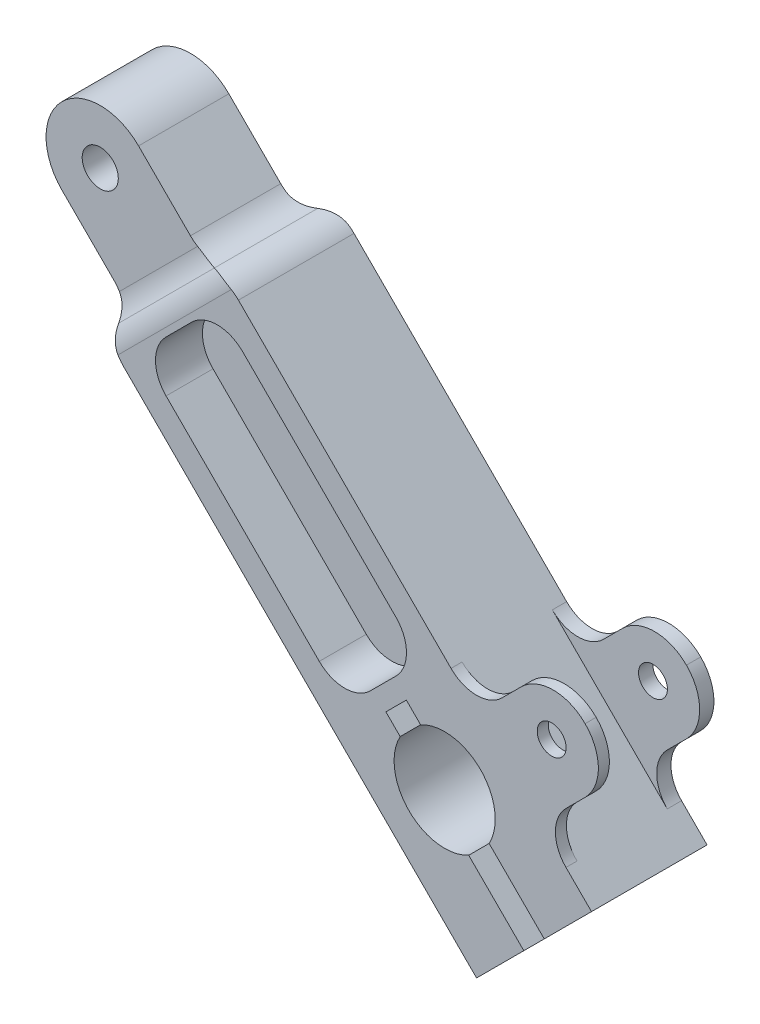
SolidWorks part; units mm, degrees
ref_plane "Front Plane" through (0, 0, 0) normal (0, 0, 1) x (1, 0, 0)
ref_plane "Top Plane" through (0, 0, 0) normal (0, 1, 0) x (1, 0, 0)
ref_plane "Right Plane" through (0, 0, 0) normal (1, 0, 0) x (0, 0, -1)
sketch "Sketch2" plane through (0, 0, 0) normal (0, 0, 1) x (1, 0, 0)
  line L0 (0, 0) -> (-234.0257, 0) construction
  line L1 (0, 0) -> (132.15, 132.15) construction
  line L2 (0, 0) -> (130.2279, -130.2279) construction
  line L3 (-10.6066, -10.6066) -> (10.6066, 10.6066) construction
  line L4 (-10.6066, -10.6066) -> (21.2132, -42.4264) construction
  line L5 (21.2132, -42.4264) -> (42.4264, -21.2132) construction
  line L6 (42.4264, -21.2132) -> (10.6066, 10.6066) construction
  line L7 (0, -21.2132) -> (21.2132, 0)
  line L9 (21.2132, 0) -> (53.033, -31.8198)
  line L10 (0, -21.2132) -> (31.8198, -53.033)
  line L11 (31.8198, -53.033) -> (26.5165, -58.3363)
  line L12 (114.318, -146.1378) -> (26.5165, -58.3363)
  line L13 (53.033, -31.8198) -> (58.3363, -26.5165)
  line L14 (128.4601, -96.6403) -> (58.3363, -26.5165)
  line L15 (146.1378, -114.318) -> (167.351, -93.1047)
  line L16 (167.351, -93.1047) -> (149.6733, -75.4271)
  line L17 (149.6733, -75.4271) -> (128.4601, -96.6403)
  line L18 (158.5121, -84.2659) -> (119.6213, -119.6213) construction
  line L19 (146.1378, -114.318) -> (160.2799, -128.4601)
  line L20 (114.318, -146.1378) -> (128.4601, -160.2799)
  line L21 (160.2799, -128.4601) -> (147.1984, -141.5416)
  line L22 (109.0147, -103.3578) -> (112.9628, -107.306)
  line L23 (103.3578, -109.0147) -> (109.0147, -103.3578)
  line L24 (103.3578, -109.0147) -> (107.306, -112.9628)
  line L25 (131.9365, -126.2797) -> (147.1984, -141.5416)
  line L26 (126.2797, -131.9365) -> (141.5416, -147.1984)
  line L27 (141.5416, -147.1984) -> (128.4601, -160.2799)
  line L28 (31.8198, -53.033) -> (53.033, -31.8198)
  line L29 (128.4601, -96.6403) -> (146.1378, -114.318)
  circle A0 centre (21.2132, -21.2132) radius 5
  circle A1 centre (149.2524, -92.6839) radius 4
  arc A2 (107.306, -112.9628) -> (126.2797, -131.9365) centre (119.6213, -119.6213) ccw
  arc A3 (131.9365, -126.2797) -> (112.9628, -107.306) centre (119.6213, -119.6213) ccw
  point P8 (0, 0)
  point P15 (10.6066, -10.6066)
  point P18 (130.2279, -130.2279)
  point P35 (111.5259, -126.9806)
  point P40 (106.1862, -106.1862)
  dimension "D4" = 10
  dimension "D5" = 15
  dimension "D12" = 8
  dimension "D13" = 12.5
  dimension "D14" = 28
  dimension "D1" = 184.17
  dimension "D2" = 30
  dimension "D3" = 45
  dimension "D6" = 15
  dimension "D7" = 30
  dimension "D8" = 45
  dimension "D9" = 45
  dimension "D10" = 30
  dimension "D11" = 25
  dimension "D15" = 20
  dimension "D17" = 19
extrude "Boss-Extrude1" add sketch "Sketch2" along normal blind 38 contours A3 L25 L21 L19 L29 L14 L13 L28 L11 L12 L20 L27 L26 A2 L24 L23 L22 region at (89.1363, -89.1363, 0)
extrude "Boss-Extrude2" add sketch "Sketch2<3>" along normal blind 6.5 contours L17 L29 L15 L16 A1 region at (139.4556, -86.4226, 0)
sketch "Sketch2<3>" plane through (0, 0, 0) normal (0, 0, 1) x (1, 0, 0) same geometry as "Sketch2"
fillet "Fillet1" radius 12.5 2 edges at (167.351, -93.1047, 3.25) (149.6733, -75.4271, 3.25)
ref_plane "Plane1" through (0, 0, 19) normal (0, 0, -1) x (-1, 0, 0)
mirror "Mirror1" about plane through (0, 0, 19) normal (0, 0, -1) of "Boss-Extrude2", "Fillet1"
sketch "Sketch3" plane through (42.4264, -42.4264, 0) normal (-0.7071, 0.7071, 0) x (0, 0, 1)
  line L0 (19, 73.5699) -> (19, -73.5699) construction
  line L1 (6.5, 15) -> (31.5, 15)
  line L2 (6.5, 15) -> (6.5, -15)
  line L3 (6.5, -15) -> (31.5, -15)
  line L4 (31.5, 15) -> (31.5, -15)
  line L5 (6.5, 15) -> (31.5, -15) construction
  line L6 (6.5, -15) -> (31.5, 15) construction
  point P0 (19, 0)
  dimension "D1" = 30
  dimension "D2" = 25
extrude "Boss-Extrude3" add sketch "Sketch3" along normal blind 45
sketch "Sketch4" plane through (0, 0, 31.5) normal (0, 0, 1) x (1, 0, 0)
  line L0 (10.6066, -10.6066) -> (31.8198, -31.8198) construction
  line L1 (0, -21.2132) -> (21.2132, 0) construction
  circle A0 centre (21.2132, -21.2132) radius 5
  dimension "D1" = 10
  dimension "D2" = 15
extrude "Cut-Extrude1" cut sketch "Sketch4" against normal through all
fillet "Fillet2" radius 15 2 edges at (21.2132, 0, 19) (0, -21.2132, 19)
sketch "Sketch5" plane through (144.37, -144.37, 0) normal (0.7071, -0.7071, 0) x (0, 0, -1)
  line L0 (-38, -13.25) -> (0, -13.25) construction
  line L1 (-38, -4) -> (-38, -22.5) construction
  line L2 (0, -4) -> (0, -22.5) construction
  circle A0 centre (-27, -13.25) radius 4
  circle A1 centre (-13, -13.25) radius 4
  dimension "D1" = 8
  dimension "D2" = 8
  dimension "D3" = 14
  dimension "D4" = 11
fillet "Fillet3" radius 10 4 edges at (128.4601, -96.6403, 34.75) (128.4601, -96.6403, 3.25) (146.1378, -114.318, 34.75) (146.1378, -114.318, 3.25)
sketch "Sketch8" plane through (-15.9099, -15.9099, 0) normal (-0.7071, -0.7071, 0) x (0, 0, 1)
  circle A0 centre (22.0722, -191.8383) radius 4.1672 construction
  circle A1 centre (22.0722, -151.8383) radius 4.1672 construction
  circle A2 centre (22.0722, -191.8383) radius 4.1672
  circle A3 centre (22.0722, -151.8383) radius 4.1672
extrude "Cut-Extrude4" cut sketch "Sketch8" against normal blind 10
sketch "Sketch9" plane through (0, 0, 0) normal (0, 0, -1) x (-1, 0, 0)
  line L0 (-128.4601, -160.2799) -> (-26.5165, -58.3363)
  line L1 (-128.4601, -160.2799) -> (-184.1342, -104.6058)
  line L2 (-26.5165, -58.3363) -> (-82.1906, -2.6622)
  line L3 (-184.1342, -104.6058) -> (-82.1906, -2.6622)
extrude "Cut-Extrude5" cut sketch "Sketch9" against normal up to surface (2.5515 mm away) contours L0 L1 L3 L2
sketch "Sketch10" plane through (0, 0, 38) normal (0, 0, 1) x (1, 0, 0)
  line L0 (128.4601, -160.2799) -> (26.5165, -58.3363)
  line L1 (128.4601, -160.2799) -> (184.01, -104.73)
  line L2 (26.5165, -58.3363) -> (82.0664, -2.7864)
  line L3 (184.01, -104.73) -> (82.0664, -2.7864)
extrude "Cut-Extrude6" cut sketch "Sketch10" against normal up to surface (3.4485 mm away)
sketch "Sketch11" plane through (0, 0, 2.5515) normal (0, 0, -1) x (-1, 0, 0)
  line L0 (-106.1862, -106.1862) -> (-42.4264, -42.4264)
  line L1 (-103.3578, -109.0147) -> (-109.0147, -103.3578) construction
  line L2 (-26.5165, -58.3363) -> (-58.3363, -26.5165) construction
  line L3 (-88.4485, -109.6617) -> (-109.6617, -88.4485)
  line L4 (-88.4485, -109.6617) -> (-38.951, -60.1642)
  line L5 (-109.6617, -88.4485) -> (-60.1642, -38.951)
  line L6 (-38.951, -60.1642) -> (-60.1642, -38.951)
  line L7 (-88.4485, -109.6617) -> (-60.1642, -38.951) construction
  line L8 (-109.6617, -88.4485) -> (-38.951, -60.1642) construction
  line L9 (-88.4485, -109.6617) -> (-109.6617, -88.4485)
  line L10 (-88.4485, -109.6617) -> (-91.984, -113.1972)
  line L11 (-109.6617, -88.4485) -> (-113.1972, -91.984)
  line L12 (-91.984, -113.1972) -> (-113.1972, -91.984)
  line L13 (-74.3063, -74.3063) -> (-63.6997, -84.9129)
  line L14 (-38.951, -60.1642) -> (-60.1642, -38.951)
  line L15 (-38.951, -60.1642) -> (-35.4154, -56.6286)
  line L16 (-60.1642, -38.951) -> (-56.6286, -35.4154)
  line L17 (-35.4154, -56.6286) -> (-56.6286, -35.4154)
  point P7 (-74.3063, -74.3063)
  dimension "D1" = 70
  dimension "D2" = 30
  dimension "D3" = 5
  dimension "D4" = 90
  dimension "D5" = 5
extrude "Cut-Extrude7" cut sketch "Sketch11" against normal blind 13 contours L4 L6 L0 L3 | L0 L6 L5 L3 | L12 L0 L3 L11 | L12 L10 L3 L0 | L13 L0 L3 L4 | L14 L15 L17 L16 region at (106.1261, -95.5195, 2.5515) region at (95.5195, -106.1261, 2.5515) region at (79.6096, -69.003, 2.5515) region at (81.3774, -91.984, 2.5515) region at (56.6286, -67.2352, 2.5515)
fillet "Fillet4" radius 10 4 edges at (91.984, -113.1972, 9.0515) (113.1972, -91.984, 9.0515) (35.4154, -56.6286, 9.0515) (56.6286, -35.4154, 9.0515)
fillet "Fillet6" radius 10 4 edges at (42.4264, -42.4264, 31.5) (31.8198, -53.033, 19) (53.033, -31.8198, 19) (42.4264, -42.4264, 6.5)
fillet "Fillet7" radius 10 4 edges at (42.4264, -42.4264, 34.5515) (58.3363, -26.5165, 18.5515) (26.5165, -58.3363, 18.5515) (42.4264, -42.4264, 2.5515)
ref_plane "Plane2" through (0, 0, 18.5515) normal (0, 0, -1) x (-1, 0, 0)
mirror "Mirror2" about plane through (0, 0, 18.5515) normal (0, 0, -1) of "Fillet4", "Cut-Extrude7"
